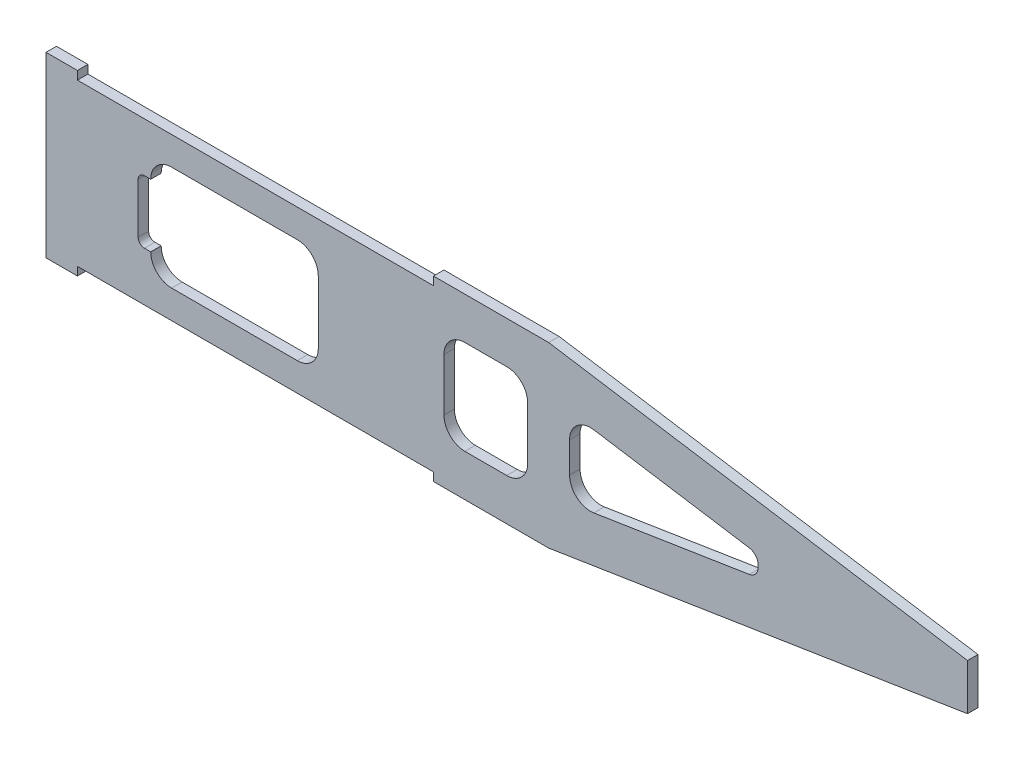
SolidWorks part; units mm, degrees
ref_plane "Ebene vorne" through (0, 0, 0) normal (0, 0, 1) x (1, 0, 0)
ref_plane "Ebene oben" through (0, 0, 0) normal (0, 1, 0) x (1, 0, 0)
ref_plane "Ebene rechts" through (0, 0, 0) normal (1, 0, 0) x (0, 0, -1)
sketch "Skizze1" plane through (0, 0, 0) normal (0, 0, 1) x (1, 0, 0)
  line L0 (0, 0) -> (440, 0) construction
  line L1 (0, 42.5) -> (0, -42.5)
  line L2 (0, -42.5) -> (240, -42.5)
  line L3 (240, -42.5) -> (440, -11)
  line L4 (440, -11) -> (440, 11)
  line L5 (240, 42.5) -> (440, 11)
  line L6 (0, 42.5) -> (240, 42.5)
  dimension "D1" = 440
  dimension "D2" = 85
  dimension "D3" = 22
  dimension "D4" = 200
extrude "Grundplatte" add sketch "Skizze1" along normal blind 5
sketch "Skizze2" plane through (0, 0, 5) normal (0, 0, 1) x (1, 0, 0)
  line L0 (50, 0) -> (44, 0) construction
  line L1 (130, 25) -> (50, 25)
  line L2 (130, 25) -> (130, -25)
  line L3 (130, -25) -> (50, -25)
  line L4 (50, 25) -> (50, 15)
  line L5 (130, 25) -> (50, -25) construction
  line L6 (130, -25) -> (50, 25) construction
  line L7 (44, -15) -> (44, 15)
  line L8 (44, 15) -> (50, 15)
  line L9 (44, -15) -> (50, -15)
  line L10 (50, -15) -> (50, -25)
  point P0 (90, 0)
  dimension "D1" = 90
  dimension "D2" = 50
  dimension "D3" = 80
  dimension "D4" = 30
  dimension "D5" = 6
extrude "Schnitt-Linear austragen1" cut sketch "Skizze2" against normal through all
fillet "Verrundung1" radius 10 4 edges at (130, 25, 2.5) (130, -25, 2.5) (50, 25, 2.5) (50, -25, 2.5)
sketch "Skizze3" plane through (0, 0, 5) normal (0, 0, 1) x (1, 0, 0)
  line L0 (0, 0) -> (440, 0) construction
  line L1 (0, 42.5) -> (0, -42.5) construction
  line L2 (440, -11) -> (440, 11) construction
  line L3 (240, 42.5) -> (0, 42.5) construction
  line L4 (15, 42.5) -> (185, 42.5)
  line L5 (15, 42.5) -> (15, 38.5)
  line L6 (15, 38.5) -> (185, 38.5)
  line L7 (185, 42.5) -> (185, 38.5)
  line L8 (185, -42.5) -> (185, -38.5)
  line L9 (15, -38.5) -> (185, -38.5)
  line L10 (15, -42.5) -> (15, -38.5)
  line L11 (15, -42.5) -> (185, -42.5)
  dimension "D1" = 4
  dimension "D2" = 170
  dimension "D3" = 15
extrude "Ausschnitt_Flächenaufdoppler" cut sketch "Skizze3" against normal through all
sketch "Skizze4" plane through (0, 0, 5) normal (0, 0, 1) x (1, 0, 0)
  line L0 (0, 0) -> (440, 0) construction
  line L1 (440, -11) -> (440, 11) construction
  line L2 (190, -22.5) -> (190, 22.5)
  line L3 (190, 22.5) -> (230, 22.5)
  line L4 (230, 22.5) -> (230, -22.5)
  line L6 (250, -19) -> (250, 19)
  line L7 (250, 19) -> (340, 4.825)
  line L8 (340, 4.825) -> (340, -4.825)
  line L9 (250, -19) -> (340, -4.825)
  line L10 (190, -22.5) -> (230, -22.5)
  line L11 (440, 11) -> (240, 42.5) construction
  line L13 (0, 42.5) -> (0, -42.5) construction
  point P14 (340, 0)
  point P17 (190, 0)
  dimension "D1" = 45
  dimension "D2" = 38
  dimension "D3" = 90
  dimension "D4" = 20
  dimension "D5" = 40
  dimension "D6" = 190
extrude "Ausschnitt Gewicht" cut sketch "Skizze4" against normal through all
fillet "Verrundung2" radius 10 6 edges at (250, -19, 2.5) (250, 19, 2.5) (190, -22.5, 2.5) (230, -22.5, 2.5) (230, 22.5, 2.5) (190, 22.5, 2.5)
fillet "Verrundung3" radius 5 2 edges at (340, -4.825, 2.5) (340, 4.825, 2.5)
fillet "Verrundung4" radius 3 2 edges at (44, -15, 2.5) (44, 15, 2.5)
